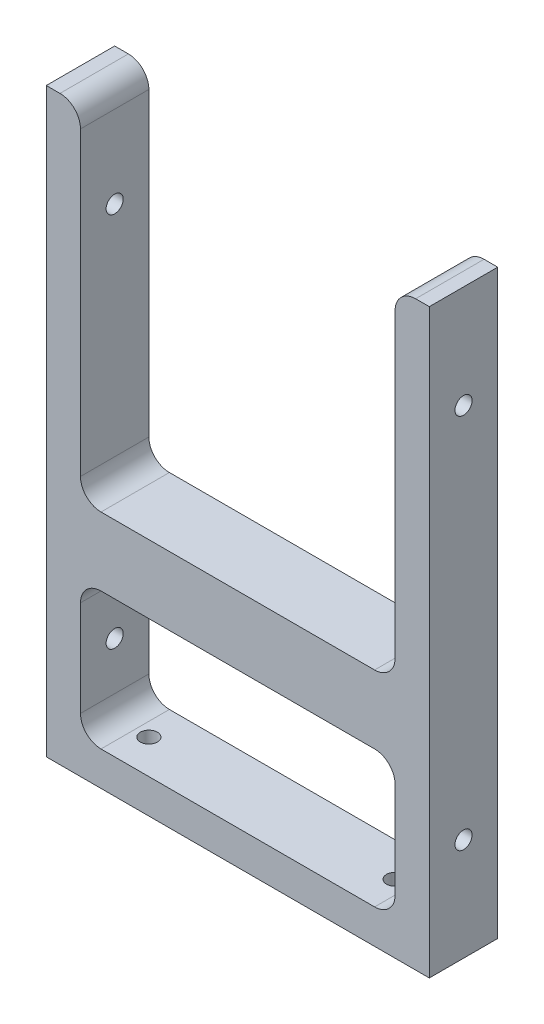
SolidWorks part; units mm, degrees
ref_plane "Спереди" through (0, 0, 0) normal (0, 0, 1) x (1, 0, 0)
ref_plane "Сверху" through (0, 0, 0) normal (0, 1, 0) x (1, 0, 0)
ref_plane "Справа" through (0, 0, 0) normal (1, 0, 0) x (0, 0, -1)
sketch "Эскиз1" plane through (0, 0, 0) normal (0, 0, 1) x (1, 0, 0)
  line L0 (-23, -17.5) -> (23, -17.5)
  line L1 (-28, 42.5) -> (-23, 42.5)
  line L2 (-28, 42.5) -> (-28, -42.5)
  line L3 (-28, -42.5) -> (28, -42.5)
  line L4 (28, 42.5) -> (28, -42.5)
  line L5 (-28, 42.5) -> (28, -42.5) construction
  line L6 (-28, -42.5) -> (28, 42.5) construction
  line L7 (23, 42.5) -> (28, 42.5)
  line L8 (-23, 42.5) -> (-23, -7.5)
  line L9 (-23, -37.5) -> (23, -37.5)
  line L10 (23, 42.5) -> (23, -7.5)
  line L13 (-23, -7.5) -> (23, -7.5)
  line L14 (-23, -17.5) -> (-23, -37.5)
  line L15 (23, -17.5) -> (23, -37.5)
  line L16 (-28, 0) -> (42.8015, 0) construction
  point P0 (0, 0)
  point P6 (0, 0)
  dimension "D1" = 56
  dimension "D2" = 85
  dimension "D3" = 5
  dimension "D4" = 5
  dimension "D5" = 10
  dimension "D6" = 20
  dimension "D7" = 5
extrude "Бобышка-Вытянуть1" add sketch "Эскиз1" along normal blind 10
fillet "Скругление1" radius 3 8 edges at (-23, -17.5, 5) (23, -17.5, 5) (23, -37.5, 5) (23, -7.5, 5) (23, 42.5, 5) (-23, -37.5, 5) (-23, -7.5, 5) (-23, 42.5, 5)
sketch "Эскиз2" plane through (0, -42.5, 0) normal (0, -1, 0) x (1, 0, 0)
  line L0 (-28, 5) -> (28, 5) construction
  line L1 (-28, 10) -> (-28, 0) construction
  line L2 (28, 10) -> (28, 0) construction
  line L3 (-18, 10) -> (-18, 0) construction
  line L4 (-28, 10) -> (28, 10) construction
  line L5 (-28, 0) -> (28, 0) construction
  line L6 (18, 10) -> (18, 0) construction
  dimension "D1" = 10
  dimension "D2" = 10
hole_wizard "Отверстие обработанное метчиком M3x0.51" positions "Эскиз4" profile "Эскиз3" tap size "M3x0.5" standard "Ansi Metric" end condition up to next
sketch "Эскиз4" plane through (0, -42.5, 0) normal (0, -1, 0) x (-1, 0, 0)
  line L0 (18, -10) -> (18, 0) construction
  line L1 (-18, -10) -> (-18, 0) construction
  point P0 (18, -5)
  point P4 (-18, -5)
sketch "Эскиз3" plane through (-18, -42.5, 5) normal (1, 0, 0) x (0, 0, -1)
  line L0 (0, 0) -> (0, 5)
  line L1 (0, 5) -> (1.25, 5)
  line L2 (1.25, 5) -> (1.25, 0)
  line L5 (1.25, 0) -> (0, 0)
  line L11 (0, -6.35) -> (0, 107.95) construction
  dimension "Диаметр проходного сверла" = 2.5
  dimension "Глубина проходного сверла" = 5
cosmetic thread "Отверстие резьбы1" parameters "D2"=3
cosmetic thread "Отверстие резьбы2" parameters "D2"=3
sketch "Эскиз5" plane through (28, 0, 0) normal (1, 0, 0) x (0, 0, -1)
  line L0 (-5, 42.5) -> (-5, -42.5) construction
  line L1 (-10, 42.5) -> (0, 42.5) construction
  line L2 (-10, -42.5) -> (0, -42.5) construction
  line L3 (0, 27.5) -> (-10, 27.5) construction
  line L4 (0, -42.5) -> (0, 42.5) construction
  line L5 (-10, -42.5) -> (-10, 42.5) construction
  line L6 (0, -27.5) -> (-10, -27.5) construction
  dimension "D1" = 15
  dimension "D2" = 15
  dimension "D3" = 55
hole_wizard "Отверстие обработанное метчиком M3x0.52" positions "Эскиз7" profile "Эскиз6" tap size "M3x0.5" standard "Ansi Metric" end condition through all
sketch "Эскиз7" plane through (28, 0, 0) normal (1, 0, 0) x (0, 0, -1)
  line L0 (0, 27.5) -> (-10, 27.5) construction
  line L1 (0, -27.5) -> (-10, -27.5) construction
  point P0 (-5, 27.5)
  point P4 (-5, -27.5)
sketch "Эскиз6" plane through (28, 27.5, 5) normal (0, 1, 0) x (0, 0, -1)
  line L0 (0, 0) -> (0, 56)
  line L1 (0, 56) -> (1.25, 56)
  line L2 (1.25, 56) -> (1.25, 0)
  line L5 (1.25, 0) -> (0, 0)
  line L11 (0, -6.35) -> (0, 107.95) construction
  dimension "Диаметр проходного сверла" = 2.5
  dimension "Глубина проходного сверла" = 56
cosmetic thread "Отверстие резьбы3" parameters "D2"=3
cosmetic thread "Отверстие резьбы4" parameters "D2"=3
